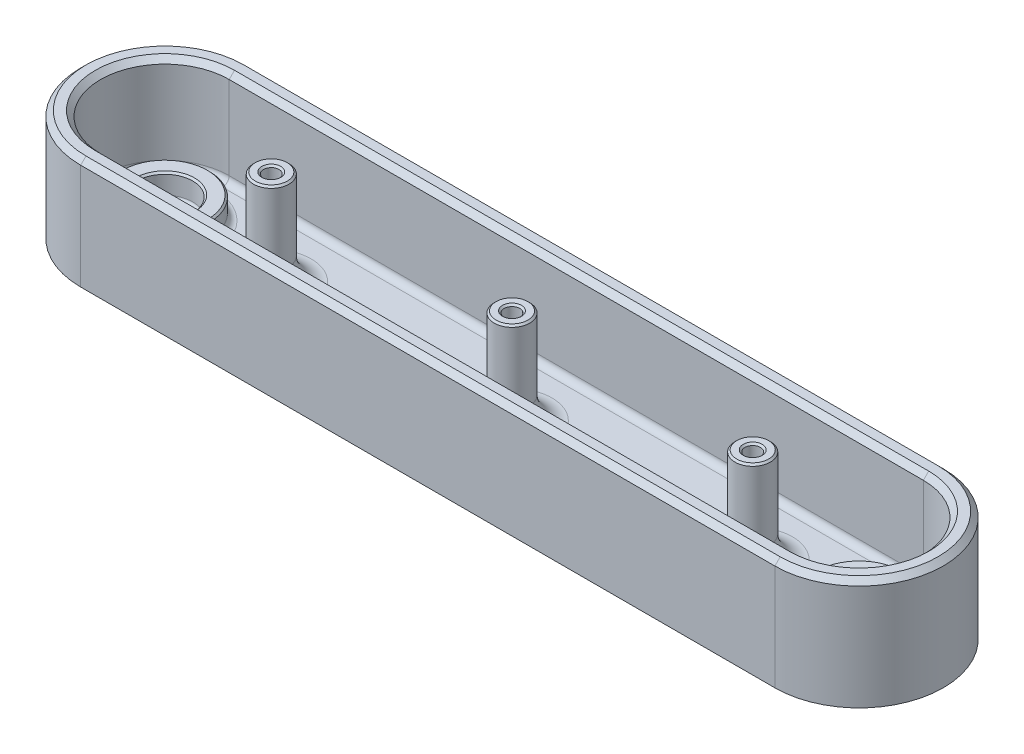
SolidWorks part; units mm, degrees
material "PLA"
ref_plane "Front Plane" through (0, 0, 0) normal (0, 0, 1) x (1, 0, 0)
ref_plane "Top Plane" through (0, 0, 0) normal (0, 1, 0) x (1, 0, 0)
ref_plane "Right Plane" through (0, 0, 0) normal (1, 0, 0) x (0, 0, -1)
sketch "Sketch1" plane through (0, 0, 0) normal (0, 1, 0) x (1, 0, 0)
  line L0 (-99.441, 0) -> (99.441, 0) construction
  line L1 (0, -55.9739) -> (0, 55.9739) construction
  line L2 (-99.441, 24.13) -> (99.441, 24.13)
  line L3 (-99.441, -24.13) -> (99.441, -24.13)
  arc A0 (-99.441, 24.13) -> (-99.441, -24.13) centre (-99.441, 0) ccw
  arc A1 (99.441, 24.13) -> (99.441, -24.13) centre (99.441, 0) cw
  point P4 (0, 0)
  point P10 (0, 0)
  dimension "D2" = 48.26
  dimension "D1" = 198.882
extrude "MainBlock" add sketch "Sketch1" along normal blind 31.75
sketch "Sketch2" plane through (0, 31.75, 0) normal (0, 1, 0) x (1, 0, 0)
  line L0 (0, 0) -> (155.7407, 0) construction
  line L1 (0, 0) -> (0, 57.4416) construction
  line L2 (-99.441, -24.13) -> (99.441, -24.13) construction
  line L3 (99.441, 24.13) -> (-99.441, 24.13) construction
  line L4 (-99.441, -24.13) -> (99.441, -24.13) construction
  line L5 (99.441, 24.13) -> (-99.441, 24.13) construction
  line L6 (-99.441, 18.415) -> (99.441, 18.415)
  line L7 (-99.441, -18.415) -> (99.441, -18.415)
  arc A0 (99.441, -24.13) -> (99.441, 24.13) centre (99.441, 0) ccw construction
  arc A1 (-99.441, 24.13) -> (-99.441, -24.13) centre (-99.441, 0) ccw construction
  arc A2 (99.441, -24.13) -> (99.441, 24.13) centre (99.441, 0) ccw construction
  arc A3 (-99.441, 24.13) -> (-99.441, -24.13) centre (-99.441, 0) ccw construction
  arc A4 (-99.441, 18.415) -> (-99.441, -18.415) centre (-99.441, 0) ccw
  arc A5 (99.441, 18.415) -> (99.441, -18.415) centre (99.441, 0) cw
  point P18 (0, 18.415)
  point P19 (0, -18.415)
  dimension "D1" = 5.715
extrude "MainPocket" cut sketch "Sketch2" against normal offset from surface (27.305 mm away) 4.445 up to face at (0, 0, 0)
sketch "Sketch3" plane through (0, 0, 0) normal (0, -1, 0) x (1, 0, 0)
  line L2 (-99.441, -24.13) -> (99.441, -24.13)
  line L3 (99.441, 24.13) -> (-99.441, 24.13)
  line L4 (-99.441, -24.13) -> (99.441, -24.13) construction
  line L5 (99.441, 24.13) -> (-99.441, 24.13) construction
  circle A0 centre (-99.441, 0) radius 4.445
  circle A1 centre (99.441, 0) radius 4.445
  arc A2 (-99.441, 24.13) -> (-99.441, -24.13) centre (-99.441, 0) ccw
  arc A3 (99.441, -24.13) -> (99.441, 24.13) centre (99.441, 0) ccw
  arc A4 (-99.441, 24.13) -> (-99.441, -24.13) centre (-99.441, 0) ccw construction
  arc A5 (99.441, -24.13) -> (99.441, 24.13) centre (99.441, 0) ccw construction
  dimension "D2" = 8.89
  dimension "D3" = 8.89
  dimension "D1" = 0
extrude "Cut-Extrude1" cut sketch "Sketch3" against normal through all
sketch "Sketch4" plane through (0, 4.445, 0) normal (0, 1, 0) x (1, 0, 0)
  line L0 (0, 0) -> (50000, 0) construction
  line L1 (0, 0) -> (0, 50000) construction
  line L2 (99.441, 18.415) -> (-99.441, 18.415)
  line L3 (-99.441, -18.415) -> (99.441, -18.415)
  line L4 (99.441, 18.415) -> (-99.441, 18.415) construction
  line L5 (-99.441, -18.415) -> (99.441, -18.415) construction
  circle A0 centre (-99.441, 0) radius 7.9566
  circle A1 centre (-99.441, 0) radius 12.7
  arc A2 (99.441, -18.415) -> (99.441, 18.415) centre (99.441, 0) ccw
  arc A3 (-99.441, 18.415) -> (-99.441, -18.415) centre (-99.441, 0) ccw
  arc A4 (99.441, -18.415) -> (99.441, 18.415) centre (99.441, 0) ccw construction
  arc A5 (-99.441, 18.415) -> (-99.441, -18.415) centre (-99.441, 0) ccw construction
  circle A6 centre (99.441, 0) radius 12.7
  circle A7 centre (99.441, 0) radius 7.9566
  dimension "D2" = 15.9131
  dimension "D3" = 25.4
  dimension "D1" = 0
extrude "Boss-Extrude1" add sketch "Sketch4" along normal blind 6.35
sketch "Sketch5" plane through (0, 0, 0) normal (0, -1, 0) x (1, 0, 0)
  line L0 (0, 0) -> (0, 50000) construction
  line L2 (-99.441, -24.13) -> (99.441, -24.13)
  line L3 (99.441, 24.13) -> (-99.441, 24.13)
  line L4 (-99.441, -24.13) -> (99.441, -24.13) construction
  line L5 (99.441, 24.13) -> (-99.441, 24.13) construction
  circle A0 centre (-99.441, 0) radius 6.35
  circle A1 centre (-99.441, 0) radius 4.445 construction
  arc A2 (-99.441, 24.13) -> (-99.441, -24.13) centre (-99.441, 0) ccw
  arc A3 (99.441, -24.13) -> (99.441, 24.13) centre (99.441, 0) ccw
  arc A4 (-99.441, 24.13) -> (-99.441, -24.13) centre (-99.441, 0) ccw construction
  arc A5 (99.441, -24.13) -> (99.441, 24.13) centre (99.441, 0) ccw construction
  circle A6 centre (-99.441, 0) radius 4.445
  circle A7 centre (99.441, 0) radius 4.445 construction
  circle A8 centre (99.441, 0) radius 6.35 construction
  dimension "D2" = 12.7
  dimension "D1" = 0
extrude "Boss-Extrude2" [suppressed] add sketch "Sketch5" along normal blind 3.81
fillet "Fillet1" [suppressed] radius 1.27
sketch "Sketch7" plane through (0, 4.445, 0) normal (0, 1, 0) x (1, 0, 0)
  line L0 (1.3556, 0) -> (50001.3556, 0) construction
  circle A0 centre (0, 0) radius 2.2225
  circle A1 centre (-68.961, 0) radius 2.2225
  circle A2 centre (-99.441, 0) radius 4.445 construction
  circle A3 centre (99.441, 0) radius 4.445 construction
  circle A4 centre (99.441, 0) radius 4.445 construction
  circle A5 centre (-99.441, 0) radius 4.445 construction
  circle A6 centre (68.961, 0) radius 2.2225
  circle A7 centre (-68.961, 0) radius 5.08
  circle A8 centre (0, 0) radius 5.08
  circle A9 centre (68.961, 0) radius 5.08
  dimension "D3" = 4.445
  dimension "D4" = 4.445
  dimension "D5" = 4.445
  dimension "D6" = 10.16
  dimension "D7" = 10.16
  dimension "D8" = 10.16
  dimension "D1" = 30.48
  dimension "D2" = 30.48
extrude "Boss-Extrude3" add sketch "Sketch7" along normal up to surface (27.305 mm away) up to face at (0, 31.75, 0)
fillet "Fillet2" radius 0.635 2 edges at (99.441, 4.445, 7.9566) (-99.441, 4.445, 7.9566)
fillet "Fillet3" radius 1.905 6 edges at (117.856, 4.445, 0) (0, 4.445, 18.415) (-117.856, 4.445, 0) (99.441, 4.445, -12.7) (-99.441, 4.445, 12.7) (0, 4.445, -18.415)
fillet "Fillet6" radius 6.35 3 edges at (68.961, 4.445, 5.08) (0, 4.445, 5.08) (-68.961, 4.445, 5.08)
sketch "Sketch9" plane through (0, 0, 0) normal (0, -1, 0) x (1, 0, 0)
  circle A0 centre (99.441, 0) radius 4.445 construction
  circle A1 centre (99.441, 0) radius 4.445
  circle A6 centre (99.441, 0) radius 5.715
  dimension "D2" = 11.43
extrude "Bearing-Spacer" [suppressed] add sketch "Sketch9" along normal blind 8.89
fillet "Fillet7" [suppressed] radius 2.54
chamfer "Chamfer1" [suppressed] distance 0.508 angle 45
chamfer "Chamfer2" distance 0.508 angle 45 12 edges at (68.961, 31.75, 2.2225) (99.441, 4.445, 4.445) (99.441, 10.795, -12.7) (99.441, 10.795, -7.9566) (-99.441, 4.445, 4.445) (-99.441, 10.795, 12.7) (-68.961, 31.75, 5.08) (0, 31.75, 5.08) (0, 31.75, 2.2225) (68.961, 31.75, 5.08) (-99.441, 10.795, 7.9566) (-68.961, 31.75, 2.2225)
chamfer "Chamfer3" distance 1.524 angle 45 8 edges at (0, 31.75, -24.13) (-123.571, 31.75, 0) (123.571, 31.75, 0) (0, 31.75, 24.13) (0, 31.75, -18.415) (-117.856, 31.75, 0) (117.856, 31.75, 0) (0, 31.75, 18.415)
chamfer "Chamfer5" [suppressed] distance 0.381 angle 45
sketch "Sketch10" plane through (0, 4.445, 0) normal (0, 1, 0) x (1, 0, 0)
  circle A0 centre (68.961, 0) radius 2.2225 construction
  circle A1 centre (0, 0) radius 2.2225 construction
  circle A2 centre (-68.961, 0) radius 2.2225 construction
  circle A3 centre (68.961, 0) radius 2.2225
  circle A4 centre (0, 0) radius 2.2225
  circle A5 centre (-68.961, 0) radius 2.2225
extrude "Boss-Extrude4" add sketch "Sketch10" along normal blind 16.51
equation "\"D5@Sketch7\"=\"D3@Sketch7\""
equation "\"D4@Sketch7\"=\"D3@Sketch7\""
equation "\"D7@Sketch7\"=\"D6@Sketch7\""
equation "\"D8@Sketch7\"=\"D6@Sketch7\""
